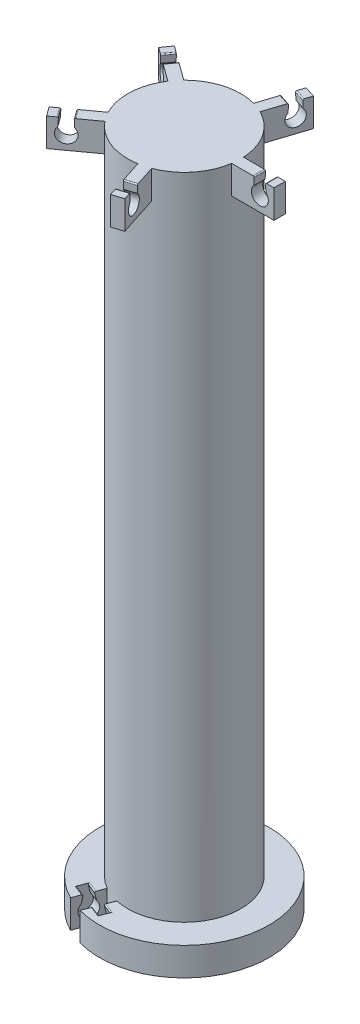
SolidWorks part; units mm, degrees
note: '?' marks a value the reader was unsure of.
ref_plane "Plan de face" through (0, 0, 0) normal (0, 0, 1) x (1, 0, 0)
ref_plane "Plan de dessus" through (0, 0, 0) normal (0, 1, 0) x (1, 0, 0)
ref_plane "Plan de droite" through (0, 0, 0) normal (1, 0, 0) x (0, 0, -1)
sketch "Esquisse1" plane through (0, 0, 0) normal (0, 1, 0) x (1, 0, 0)
  circle A0 centre (0, 0) radius 10
  dimension "D1" = 20
extrude "BASE" add sketch "Esquisse1" against normal blind 120
sketch "Esquisse2" plane through (0, 0, 0) normal (0, 1, 0) x (1, 0, 0)
  line L0 (9.3808, -1.5) -> (17.3808, -1.5)
  line L1 (17.3808, -1.5) -> (17.3808, 0.5)
  line L2 (17.3808, 0.5) -> (9.4868, 0.5)
  arc A1 (9.3808, -1.5) -> (9.4868, 0.5) centre (0, 0) ccw
  dimension "D1" = 8
  dimension "D2" = 19
  dimension "D3" = 2
extrude "BOSS - BALEINE" add sketch "Esquisse2" against normal blind 5 contours A1 L0 L1 L2
sketch "Esquisse3" plane through (0, 0, 1.5) normal (0, 0, 1) x (1, 0, 0)
  line L0 (12.3808, 0) -> (17.3808, -5) construction
  line L1 (17.3808, -5) -> (17.3808, -2.5) construction
  line L3 (17.3808, -5) -> (17.3808, 0) construction
  line L4 (17.3808, -2.5) -> (14.8808, -2.5) construction
  line L5 (14.8808, -2.5) -> (17.3808, 0) construction
  line L6 (13.8202, -1.4393) -> (13.8808, 0)
  line L7 (9.8869, 0) -> (17.3808, 0) construction
  line L8 (15.9415, -1.4393) -> (15.8808, 0)
  arc A0 (13.8202, -1.4393) -> (15.9415, -1.4393) centre (14.8808, -2.5) ccw
  point P4 (14.8808, 0)
  dimension "D1" = 3
  dimension "D2" = 5
  dimension "D3" = 1
  dimension "D4" = 1
extrude "VIDE - BALEINE" cut sketch "Esquisse3" against normal up to surface (3 mm away)
ref_axis "AXE CYLINDRE" through (0, -120, 0) along (0, 1, 0)?
pattern_circular "REP - SUPPORT BALEINE" count 5 over 360 about axis through (0, 0, 0) along (0, 1, 0) of "BOSS - BALEINE", "VIDE - BALEINE"
fillet "CONGE BALEINE" radius 0.2 10 edges at (4.7649, 0, -13.0469) (5.383, 0, -14.9491) (-10.9359, 0, -8.5635) (-12.554, 0, -9.739) (-13.1418, 0, 8.93) (-11.5237, 0, 7.7544) (3.8139, 0, 13.356) (4.4319, 0, 15.2581) (15.8808, 0, 0.5) (13.8808, 0, 0.5)
sketch "Esquisse4" plane through (0, -120, 0) normal (0, -1, 0) x (1, 0, 0)
  line L0 (0, 0) -> (-6.1591, 15.9277) construction
  line L1 (-7.7862, 6.275) -> (1.6286, 9.8665) construction
  line L2 (-4.8092, 8.2777) -> (-6.7819, 13.3793)
  line L3 (-3.134, 8.0497) -> (-3.0788, 8.0707)
  line L5 (-3.9838, 14.4613) -> (-2.0111, 9.3597)
  arc A1 (-6.7819, 13.3793) -> (-3.9838, 14.4613) centre (0, 0) ccw
  circle A2 centre (0, 0) radius 9.5733
  point P1 (-7.7862, 6.275)
  point P5 (1.6286, 9.8665)
  point P10 (-3.0796, 7.9639)
  dimension "D1" = 30
  dimension "D2" = 1.5
  dimension "D3" = 1.5
extrude "Boss.-Extru.3" add sketch "Esquisse4" against normal blind 5
sketch "Esquisse5" plane through (-1.399, 0, -0.541) normal (0.9327, 0, 0.3607) x (0.3607, 0, -0.9327)
  line L0 (-9.8869, -115) -> (-14.9248, -120) construction
  line L1 (-14.9248, -120) -> (-12.4714, -120) construction
  line L2 (-9.8869, -120) -> (-14.9248, -120) construction
  line L3 (-12.4714, -120) -> (-12.4058, -117.5) construction
  line L4 (-14.9248, -115) -> (-12.4058, -117.5) construction
  line L5 (-13.4705, -116.4434) -> (-13.1558, -115)
  line L6 (-9.8869, -115) -> (-14.9248, -115) construction
  line L7 (-13.1558, -115) -> (-11.6558, -115)
  line L8 (-11.6558, -115) -> (-11.3412, -116.4434)
  line L9 (-12.4058, -117.5) -> (-12.4058, -114.5403) construction
  arc A0 (-13.4705, -116.4434) -> (-11.3412, -116.4434) centre (-12.4058, -117.5) ccw
  dimension "D1" = 3
  dimension "D2" = 0.75
  dimension "D3" = 0.75
extrude "Enlèv. mat.-Extru.1" cut sketch "Esquisse5" against normal blind 2
fillet "Congé1" radius 0.2 2 edges at (-7.0766, -115, 11.3687) (-6.5356, -115, 9.9697)
ref_plane "SYM PIED BLOC" through (0, 0, 0) normal (0.9327, 0, 0.3607) x (0.3607, 0, -0.9327)
mirror "SYM VIDE BLOC" about plane through (0, 0, 0) normal (0.9327, 0, 0.3607) of "Enlèv. mat.-Extru.1", "Congé1"
